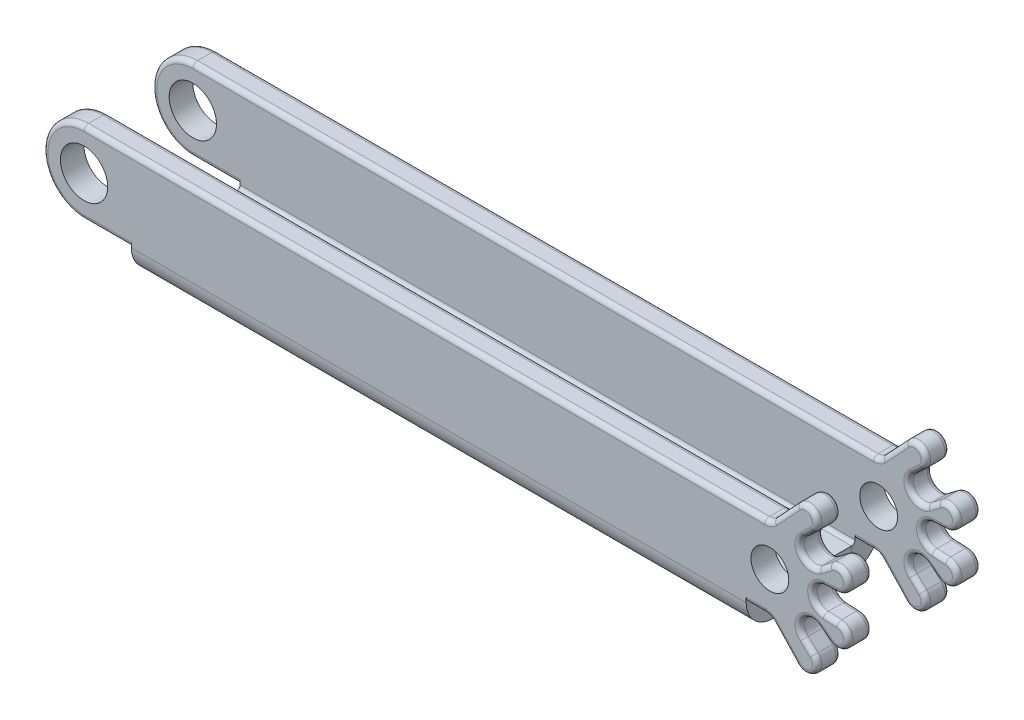
SolidWorks part; units mm, degrees
note: The reader was unsure of these and kept them because the rebuilt part matched: flange length of "Edge-Flange1".
ref_plane "Front Plane" through (0, 0, 0) normal (0, 0, 1) x (1, 0, 0)
ref_plane "Top Plane" through (0, 0, 0) normal (0, 1, 0) x (1, 0, 0)
ref_plane "Right Plane" through (0, 0, 0) normal (1, 0, 0) x (0, 0, -1)
sketch "Sketch1" plane through (0, 0, 0) normal (0, 1, 0) x (1, 0, 0)
  line L1 (-65, 14) -> (65, 14)
  line L2 (-65, 14) -> (-65, -14)
  line L3 (-65, -14) -> (65, -14)
  line L4 (65, 14) -> (65, -14)
  line L5 (-65, 14) -> (65, -14) construction
  line L6 (-65, -14) -> (65, 14) construction
  point P0 (0, 0)
  dimension "D1" = 28
  dimension "D2" = 130
base flange "Base-Flange1" sketch "Sketch1" thickness 5 reverse thickness direction no parameters "D1"=0.7366
edge flange "Edge-Flange1" sketch "Sketch10" flange profiles "Sketch10", "Sketch11" flange angle 90 flange length 23 flange position material inside bend radius 0.7366 thickness 5 relief rectangular parameters "D6"=10, "D8"=1
sketch "Sketch10" plane through (0, 0, 14) normal (0, 0, 1) x (1, 0, 0)
  line L0 (-65, 0) -> (65, 0) construction
  line L1 (-65, 0) -> (65, 0)
  line L2 (-65, 0) -> (-65, 18)
  line L3 (-65, 18) -> (65, 18)
  line L4 (65, 18) -> (65, 0)
sketch "Sketch11" plane through (0, 0, -14) normal (0, 0, -1) x (-1, 0, 0)
  line L0 (-65, 0) -> (65, 0) construction
  line L1 (-65, 0) -> (65, 0)
  line L2 (-65, 0) -> (-65, 18)
  line L3 (-65, 18) -> (65, 18)
  line L4 (65, 18) -> (65, 0)
bend "EdgeBend1" bend radius 0.7366 bend angle 90 parameters "D5"=1
bend "EdgeBend2" bend radius 0.7366 bend angle 90 parameters "D5"=2
sketch "Sketch15" plane through (0, 0, 14) normal (0, 0, 1) x (1, 0, 0)
  line L1 (-65, 18) -> (-65, 0.7366) construction
  line L2 (-75, 18) -> (-65, 18)
  line L3 (-65, 18) -> (-65, 0.7366)
  line L4 (-65, 0.7366) -> (-75, 0.7366)
  arc A0 (-75, 18) -> (-75, 0.7366) centre (-75, 9.3683) ccw
  circle A1 centre (-75, 9.3683) radius 5
  point P8 (-65, 9.3683)
  dimension "D1" = 10
  dimension "D2" = 10
extrude "Boss-Extrude1" add sketch "Sketch15" against normal blind 5 contours A1
mirror "Mirror3" about plane through (0, 0, 0) normal (0, 0, 1) of "Boss-Extrude1"
sketch "Sketch16" plane through (0, 0, 14) normal (0, 0, 1) x (1, 0, 0)
  line L0 (65, 18) -> (70, 18)
  line L1 (70, 9.3683) -> (91.4551, -27.793) construction
  line L2 (70, 9.3683) -> (91.4551, 46.5296) construction
  line L3 (35.0206, 9.3683) -> (142.7481, 9.3683) construction
  line L4 (70, 9.3683) -> (104.0826, -3.0368) construction
  line L5 (70, 9.3683) -> (104.0826, 21.7734) construction
  line L6 (70, 9.3683) -> (94.6256, -11.295) construction
  line L7 (70, 9.3683) -> (87.3049, 23.8889) construction
  line L8 (79.1969, 20.5228) -> (77.1126, 18.5962)
  line L9 (80.3228, 14.7704) -> (82.5821, 16.4885)
  line L10 (81.3802, 11.8654) -> (84.2152, 12.0015)
  line L11 (77.1126, 0.1404) -> (79.1969, -1.7862)
  line L12 (80.3228, 3.9662) -> (82.5821, 2.2481)
  line L13 (81.3802, 6.8712) -> (84.2152, 6.7351)
  line L16 (65, 18) -> (65, 0.7366)
  line L17 (70, 18) -> (75.6742, 24.0664)
  line L18 (65, 0.7366) -> (70, 0.7366)
  line L19 (70, 0.7366) -> (75.6742, -5.3298)
  circle A0 centre (70, 9.3683) radius 17.5 construction
  circle A1 centre (70, 9.3683) radius 14 construction
  circle A2 centre (70, 9.3683) radius 15 construction
  arc A3 (84.2152, 12.0015) -> (82.5821, 16.4885) centre (84.0954, 14.4986) ccw
  arc A4 (79.1969, 20.5228) -> (75.6742, 24.0664) centre (77.5, 22.3587) ccw
  arc A5 (82.5821, 2.2481) -> (84.2152, 6.7351) centre (84.0954, 4.238) ccw
  arc A6 (75.6742, -5.3298) -> (79.1969, -1.7862) centre (77.5, -3.6221) ccw
  circle A7 centre (70, 9.3683) radius 11.5 construction
  arc A8 (77.1126, 18.5962) -> (80.3228, 14.7704) centre (78.8095, 16.7604) ccw
  arc A9 (81.3802, 11.8654) -> (81.3802, 6.8712) centre (81.5, 9.3683) ccw
  arc A10 (80.3228, 3.9662) -> (77.1126, 0.1404) centre (78.8095, 1.9762) ccw
  point P21 (65, 9.3683)
  dimension "D1" = 35
  dimension "D2" = 28
  dimension "D5" = 30
  dimension "D6" = 23
  dimension "D3" = 120
  dimension "D4" = 40
  dimension "D7" = 20
  dimension "D8" = 20
  dimension "D9" = 5
extrude "Boss-Extrude2" add sketch "Sketch16" against normal blind 5
sketch "Sketch17" plane through (0, 0, 14) normal (0, 0, 1) x (1, 0, 0)
  circle A0 centre (70, 9.3683) radius 4
  dimension "D1" = 8
extrude "Cut-Extrude2" cut sketch "Sketch17" against normal blind 5 normal cut yes
mirror "Mirror5" about plane through (0, 0, 0) normal (0, 0, 1) of "Cut-Extrude2", "Boss-Extrude2"
fillet "Fillet3" radius 2.5 4 edges at (70, 0.7366, -11.5) (70, 18, -11.5) (70, 18, 11.5) (70, 0.7366, 11.5)
fillet "Fillet4" radius 1 84 edges at (66.9576, 0.7366, 9) (73.2076, 21.4293, 9) (79.273, 24.1212, 9) (78.1548, 19.5595, 9) (76.8944, 15.1534, 9) (81.4525, 15.6295, 9) (86.4446, 15.3537, 9) (82.7977, 11.9335, 9) (79, 9.3683, 9) (82.7977, 6.8031, 9) (86.4446, 3.3829, 9) (81.4525, 3.1071, 9) (76.8944, 3.5832, 9) (78.1548, -0.8229, 9) (79.273, -5.3846, 9) (79.273, -5.3846, 14) (78.1548, -0.8229, 14) (76.8944, 3.5832, 14) (81.4525, 3.1071, 14) (86.4446, 3.3829, 14) (82.7977, 6.8031, 14) (79, 9.3683, 14) (82.7977, 11.9335, 14) (86.4446, 15.3537, 14) (81.4525, 15.6295, 14) (76.8944, 15.1534, 14) (78.1548, 19.5595, 14) (79.273, 24.1212, 14) (73.2076, 21.4293, 14) (66.9576, 0.7366, 14) (79.273, -5.3846, -14) (78.1548, -0.8229, -14) (76.8944, 3.5832, -14) (81.4525, 3.1071, -14) (86.4446, 3.3829, -14) (82.7977, 6.8031, -14) (79, 9.3683, -14) (82.7977, 11.9335, -14) (86.4446, 15.3537, -14) (81.4525, 15.6295, -14) (76.8944, 15.1534, -14) (78.1548, 19.5595, -14) (79.273, 24.1212, -14) (73.2076, 21.4293, -14) (66.9576, 0.7366, -14) (79.273, -5.3846, -9) (78.1548, -0.8229, -9) (76.8944, 3.5832, -9) (81.4525, 3.1071, -9) (86.4446, 3.3829, -9) (82.7977, 6.8031, -9) (79, 9.3683, -9) (82.7977, 11.9335, -9) (86.4446, 15.3537, -9) (81.4525, 15.6295, -9) (76.8944, 15.1534, -9) (78.1548, 19.5595, -9) (79.273, 24.1212, -9) (73.2076, 21.4293, -9) (66.9576, 0.7366, -9) (-3.0424, 18, 9) (-3.0424, 18, 14) (73.2076, -2.6927, 14) (73.2076, -2.6927, 9) (73.2076, -2.6927, -14) (73.2076, -2.6927, -9) (69.9104, 18.2066, 14) (69.9104, 18.2066, 9) (69.9104, 0.53, 14) (69.9104, 0.53, 9) (69.9104, 0.53, -14) (69.9104, 0.53, -9) (69.9104, 18.2066, -14) (69.9104, 18.2066, -9) (-3.0424, 18, -14) (-3.0424, 18, -9) (-70, 0.7366, 9) (-83.6317, 9.3683, 9) (-70, 0.7366, 14) (-83.6317, 9.3683, 14) (-70, 0.7366, -9) (-83.6317, 9.3683, -9) (-70, 0.7366, -14) (-83.6317, 9.3683, -14)
sketch "Bend-Lines1" [suppressed] plane through (0, 0, 0) normal (0, 1, 0) x (1, 0, 0)
sketch "Bounding-Box1" [suppressed] plane through (0, 0, 0) normal (0, 1, 0) x (1, 0, 0)
sheet metal parameters "Sheet-Metal1" thickness 5 parameters "D1"=0.7366
flat pattern "Flat-Pattern1" [suppressed]
sketch "Bend-Lines2" plane through (0, 0, 0) normal (0, 1, 0) x (1, 0, 0)
sketch3d "Bounding-Box2" [suppressed]
  line L0 (-72.5, -19, 0) -> (72.5, -19, 0) construction
  line L1 (-72.5, 19, 0) -> (72.5, 19, 0) construction
  line L2 (-72.5, -19, 0) -> (-72.5, 19, 0) construction
  line L3 (72.5, -19, 0) -> (72.5, 19, 0) construction
sheet metal parameters "Sheet-Metal2" thickness 5 parameters "D1"=0.7366
flat pattern "Flat-Pattern1"
sketch "Bend-Lines2" plane through (0, 0, 0) normal (0, 1, 0) x (1, 0, 0)
  line L0 (72.5, 15.8054) -> (-72.5, 15.8054) construction
  line L1 (-72.5, -15.8054) -> (72.5, -15.8054) construction
  line L2 (72.5, 15.8054) -> (-72.5, 15.8054) construction
  line L3 (-72.5, -15.8054) -> (72.5, -15.8054) construction
sketch3d "Bounding-Box2" [suppressed]
  line L0 (72.5, -35.6108, 0) -> (-72.5, -35.6108, 0) construction
  line L1 (72.5, 35.6108, 0) -> (-72.5, 35.6108, 0) construction
  line L2 (72.5, -35.6108, 0) -> (72.5, 35.6108, 0) construction
  line L3 (-72.5, -35.6108, 0) -> (-72.5, 35.6108, 0) construction
bend of the flat pattern "Flatten-<EdgeBend1>1"
bend of the flat pattern "Flatten-<EdgeBend2>1"
sheet metal parameters "Sheet-Metal3" thickness 5 parameters "D1"=0.7366
flat pattern "Flat-Pattern1"
sketch "Bend-Lines2" plane through (0, 0, 0) normal (0, 1, 0) x (1, 0, 0)
  line L0 (67.5, 15.8054) -> (-67.5, 15.8054) construction
  line L1 (-67.5, -15.8054) -> (67.5, -15.8054) construction
  line L2 (67.5, 15.8054) -> (-67.5, 15.8054) construction
  line L3 (-67.5, -15.8054) -> (67.5, -15.8054) construction
sketch3d "Bounding-Box2" [suppressed]
  line L0 (-86.1316, -35.6108, 0) -> (67.5, -35.6108, 0) construction
  line L1 (-86.1316, 35.6108, 0) -> (67.5, 35.6108, 0) construction
  line L2 (-86.1316, -35.6108, 0) -> (-86.1316, 35.6108, 0) construction
  line L3 (67.5, -35.6108, 0) -> (67.5, 35.6108, 0) construction
bend of the flat pattern "Flatten-<EdgeBend1>1"
bend of the flat pattern "Flatten-<EdgeBend2>1"
sheet metal parameters "Sheet-Metal7" thickness 5 parameters "D1"=0.7366
flat pattern "Flat-Pattern1"
sketch "Bend-Lines2" plane through (0, 0, 0) normal (0, 1, 0) x (1, 0, 0)
  line L0 (67.5, 15.8054) -> (-67.5, 15.8054) construction
  line L1 (-67.5, -15.8054) -> (67.5, -15.8054) construction
  line L2 (67.5, 15.8054) -> (-67.5, 15.8054) construction
  line L3 (-67.5, -15.8054) -> (67.5, -15.8054) construction
sketch3d "Bounding-Box2" [suppressed]
  line L0 (-86.1316, -35.6108, 0) -> (67.5, -35.6108, 0) construction
  line L1 (-86.1316, 35.6108, 0) -> (67.5, 35.6108, 0) construction
  line L2 (-86.1316, -35.6108, 0) -> (-86.1316, 35.6108, 0) construction
  line L3 (67.5, -35.6108, 0) -> (67.5, 35.6108, 0) construction
bend of the flat pattern "Flatten-<EdgeBend1>1"
bend of the flat pattern "Flatten-<EdgeBend2>1"
sheet metal parameters "Sheet-Metal8" thickness 5 parameters "D1"=0.7366
flat pattern "Flat-Pattern1"
sketch "Bend-Lines2" plane through (0, 0, 0) normal (0, 1, 0) x (1, 0, 0)
  line L0 (67.5, 15.8054) -> (-67.5, 15.8054) construction
  line L1 (-67.5, -15.8054) -> (67.5, -15.8054) construction
  line L2 (67.5, 15.8054) -> (-67.5, 15.8054) construction
  line L3 (-67.5, -15.8054) -> (67.5, -15.8054) construction
sketch3d "Bounding-Box2" [suppressed]
  line L0 (-86.1316, -42.4695, 0) -> (84.0954, -42.4695, 0) construction
  line L1 (-86.1316, 35.6108, 0) -> (84.0954, 35.6108, 0) construction
  line L2 (-86.1316, -42.4695, 0) -> (-86.1316, 35.6108, 0) construction
  line L3 (84.0954, -42.4695, 0) -> (84.0954, 35.6108, 0) construction
bend of the flat pattern "Flatten-<EdgeBend1>1"
bend of the flat pattern "Flatten-<EdgeBend2>1"
sheet metal parameters "Sheet-Metal9" thickness 5 parameters "D1"=0.7366
flat pattern "Flat-Pattern1"
sketch "Bend-Lines2" plane through (0, 0, 0) normal (0, 1, 0) x (1, 0, 0)
  line L0 (67.5, 15.8054) -> (-67.5, 15.8054) construction
  line L1 (-67.5, -15.8054) -> (67.5, -15.8054) construction
  line L2 (67.5, 15.8054) -> (-67.5, 15.8054) construction
  line L3 (-67.5, -15.8054) -> (67.5, -15.8054) construction
sketch3d "Bounding-Box2" [suppressed]
  line L0 (-86.1316, -42.4695, 0) -> (84.0954, -42.4695, 0) construction
  line L1 (-86.1316, 35.6108, 0) -> (84.0954, 35.6108, 0) construction
  line L2 (-86.1316, -42.4695, 0) -> (-86.1316, 35.6108, 0) construction
  line L3 (84.0954, -42.4695, 0) -> (84.0954, 35.6108, 0) construction
bend of the flat pattern "Flatten-<EdgeBend1>1"
bend of the flat pattern "Flatten-<EdgeBend2>1"
sheet metal parameters "Sheet-Metal10" thickness 5 parameters "D1"=0.7366
flat pattern "Flat-Pattern1"
sketch "Bend-Lines2" plane through (0, 0, 0) normal (0, 1, 0) x (1, 0, 0)
  line L0 (65, 10.8054) -> (-65, 10.8054) construction
  line L1 (-65, -10.8054) -> (65, -10.8054) construction
  line L2 (65, 10.8054) -> (-65, 10.8054) construction
  line L3 (-65, -10.8054) -> (65, -10.8054) construction
sketch3d "Bounding-Box2" [suppressed]
  line L0 (-83.6317, -37.4695, 0) -> (86.5954, -37.4695, 0) construction
  line L1 (-83.6317, 37.4695, 0) -> (86.5954, 37.4695, 0) construction
  line L2 (-83.6317, -37.4695, 0) -> (-83.6317, 37.4695, 0) construction
  line L3 (86.5954, -37.4695, 0) -> (86.5954, 37.4695, 0) construction
bend of the flat pattern "Flatten-<EdgeBend1>1"
bend of the flat pattern "Flatten-<EdgeBend2>1"
